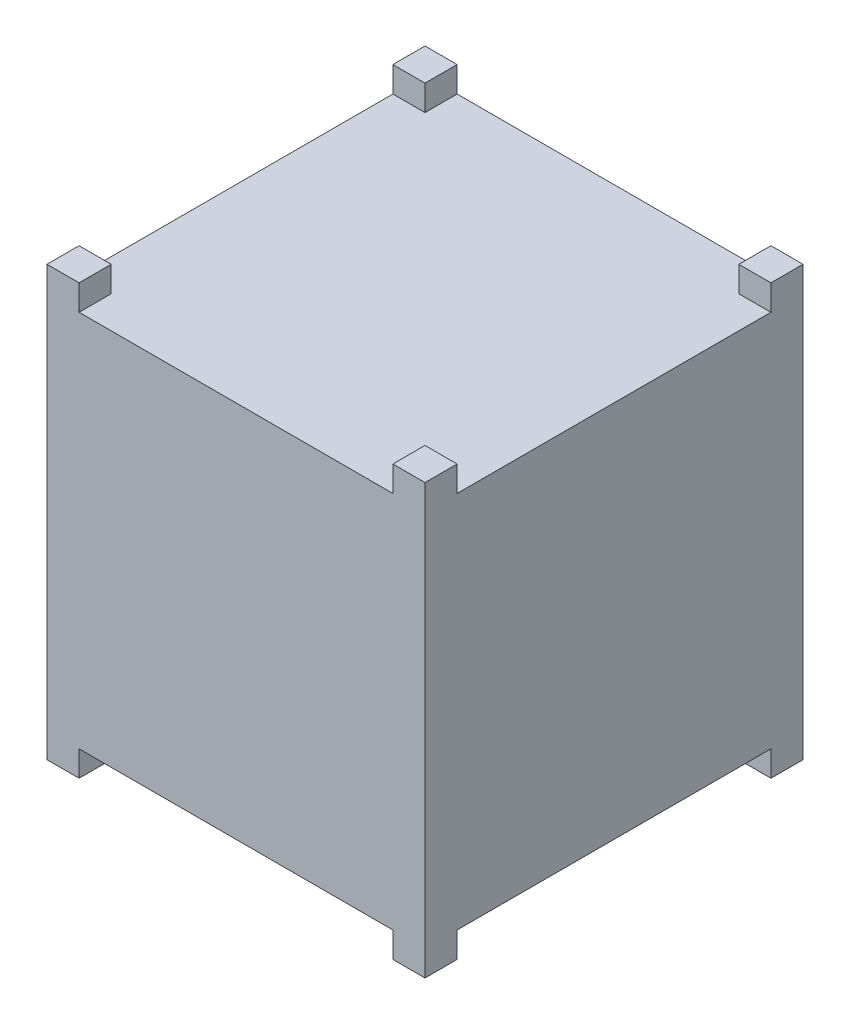
SolidWorks part; units mm, degrees
ref_plane "Front Plane" through (0, 0, 0) normal (0, 0, 1) x (1, 0, 0)
ref_plane "Top Plane" through (0, 0, 0) normal (0, 1, 0) x (1, 0, 0)
ref_plane "Right Plane" through (0, 0, 0) normal (1, 0, 0) x (0, 0, -1)
sketch "Sketch1" plane through (0, 0, 0) normal (0, 1, 0) x (1, 0, 0)
  line L1 (0, 0) -> (100, 0)
  line L2 (0, 0) -> (0, 100)
  line L3 (0, 100) -> (100, 100)
  line L4 (100, 0) -> (100, 100)
  dimension "D1" = 100
  dimension "D2" = 100
extrude "Boss-Extrude1" add sketch "Sketch1" along normal blind 113.5
sketch "Sketch2" plane through (0, 113.5, 0) normal (0, 1, 0) x (1, 0, 0)
  line L1 (0, 100) -> (8.5, 100)
  line L2 (0, 100) -> (0, 91.5)
  line L3 (0, 91.5) -> (8.5, 91.5)
  line L4 (8.5, 100) -> (8.5, 91.5)
  line L5 (100, 100) -> (91.5, 100)
  line L6 (100, 100) -> (100, 91.5)
  line L7 (100, 91.5) -> (91.5, 91.5)
  line L8 (91.5, 100) -> (91.5, 91.5)
  line L9 (100, 0) -> (91.5, 0)
  line L10 (100, 0) -> (100, 8.5)
  line L11 (100, 8.5) -> (91.5, 8.5)
  line L12 (91.5, 0) -> (91.5, 8.5)
  line L13 (0, 0) -> (8.5, 0)
  line L14 (0, 0) -> (0, 8.5)
  line L15 (0, 8.5) -> (8.5, 8.5)
  line L16 (8.5, 0) -> (8.5, 8.5)
  line L17 (0, 100) -> (100, 100)
  line L18 (0, 100) -> (0, 0)
  line L19 (0, 0) -> (100, 0)
  line L20 (100, 100) -> (100, 0)
  line M17 (0, 100) -> (0, 0)
  line M18 (0, 0) -> (100, 0)
  line M19 (100, 0) -> (100, 100)
  line M20 (100, 100) -> (0, 100)
  dimension "D1" = 8.5
extrude "Cut-Extrude1" cut sketch "Sketch2" against normal blind 6.75 contours L16 L12 L11 L7 L8 L4 L3 L15 M18 M19 M20 M17 region at (50, 113.5, -50)
extrude "Cut-Extrude2" cut sketch "Sketch2<3>" along normal blind 6.75 from surface contours L16 L12 L11 L7 L8 L4 L3 L15 M18 M19 M20 M17 region at (50, 113.5, -50) starting at face at (50, 0, -50)
sketch "Sketch2<3>" plane through (0, 113.5, 0) normal (0, 1, 0) x (1, 0, 0) same geometry as "Sketch2"
